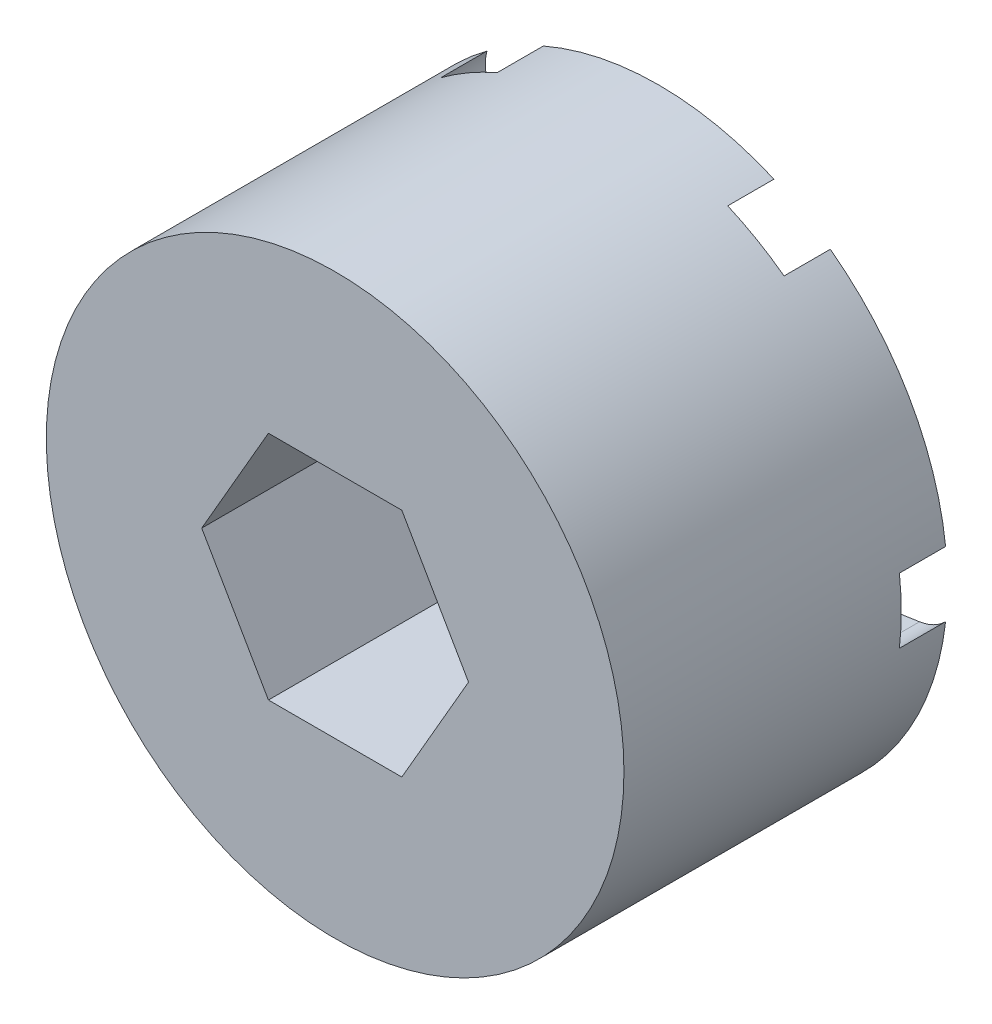
SolidWorks part; units mm, degrees
ref_plane "Front Plane" through (0, 0, 0) normal (0, 0, 1) x (1, 0, 0)
ref_plane "Top Plane" through (0, 0, 0) normal (0, 1, 0) x (1, 0, 0)
ref_plane "Right Plane" through (0, 0, 0) normal (1, 0, 0) x (0, 0, -1)
sketch "Sketch1" plane through (0, 0, 0) normal (0, 0, 1) x (1, 0, 0)
  arc A0 (0, 15.875) -> (0, -15.875) centre (0, 0) ccw
  arc A1 (0, -15.875) -> (0, 15.875) centre (0, 0) ccw
  dimension "D1" = 15.875
extrude "Boss-Extrude1" add sketch "Sketch1" along normal mid plane 17.78 contours A0 A1
sketch "Sketch2" plane through (0, 0, 8.89) normal (0, 0, 1) x (1, 0, 0)
  line L8 (7.3323, 0) -> (3.6662, 6.35)
  line L9 (3.6662, 6.35) -> (-3.6662, 6.35)
  line L11 (-3.6662, 6.35) -> (-7.3323, 0)
  line L12 (-7.3323, 0) -> (-3.6662, -6.35)
  line L13 (-3.6662, -6.35) -> (3.6662, -6.35)
  line L14 (3.6662, -6.35) -> (7.3323, 0)
  circle A0 centre (0, 0) radius 6.35 construction
  dimension "D1" = 12.7
extrude "Cut-Extrude1" cut sketch "Sketch2" against normal blind 10.16 contours L9 L11 L12 L13 L14 L8
sketch "Sketch4" plane through (0, 0, -8.89) normal (0, 0, -1) x (-1, 0, 0)
  line L0 (-6.3791, 3.683) -> (-9.346, 11.1618)
  line L1 (-4.9934, 13.6748) -> (0, 7.366)
  line L2 (0, 7.366) -> (4.9934, 13.6748)
  line L3 (9.346, 11.1618) -> (6.3791, 3.683)
  line L4 (6.3791, 3.683) -> (14.3394, 2.513)
  line L5 (14.3394, -2.513) -> (6.3791, -3.683)
  line L6 (6.3791, -3.683) -> (9.346, -11.1618)
  line L7 (-14.3394, 2.513) -> (-6.3791, 3.683)
  line L8 (-14.3394, -2.513) -> (-6.3791, -3.683)
  line L9 (-6.3791, -3.683) -> (-9.346, -11.1618)
  line L10 (-4.9934, -13.6748) -> (0, -7.366)
  line L11 (0, -7.366) -> (4.9934, -13.6748)
  line L12 (-6.3791, -3.683) -> (-6.3791, 3.683) construction
  line L13 (-6.3791, 3.683) -> (0, 7.366) construction
  line L14 (6.3791, 3.683) -> (0, 7.366) construction
  line L15 (6.3791, -3.683) -> (6.3791, 3.683) construction
  line L16 (0, -7.366) -> (6.3791, -3.683) construction
  line L17 (0, -7.366) -> (-6.3791, -3.683) construction
  line L18 (-6.3791, 3.683) -> (6.3791, -3.683) construction
  arc A0 (-9.346, 11.1618) -> (-4.9934, 13.6748) centre (-6.985, 12.0984) cw
  arc A1 (-14.3394, -2.513) -> (-14.3394, 2.513) centre (-13.97, 0) cw
  arc A2 (-9.346, -11.1618) -> (-4.9934, -13.6748) centre (-6.985, -12.0984) ccw
  arc A3 (4.9934, -13.6748) -> (9.346, -11.1618) centre (6.985, -12.0984) ccw
  arc A4 (14.3394, 2.513) -> (14.3394, -2.513) centre (13.97, 0) cw
  arc A5 (4.9934, 13.6748) -> (9.346, 11.1618) centre (6.985, 12.0984) cw
  point P24 (0, 0)
  point P25 (8.255, 14.2981)
  dimension "D1" = 2.54
  dimension "D2" = 7.366
  dimension "D3" = 16.51
  dimension "D4" = 120
  dimension "D5" = 120
  dimension "D6" = 120
extrude "Cut-Extrude2" cut sketch "Sketch4" against normal blind 2.54
ref_axis "Axis1" through (0, 0, 8.89) along (0, 0, -1)
